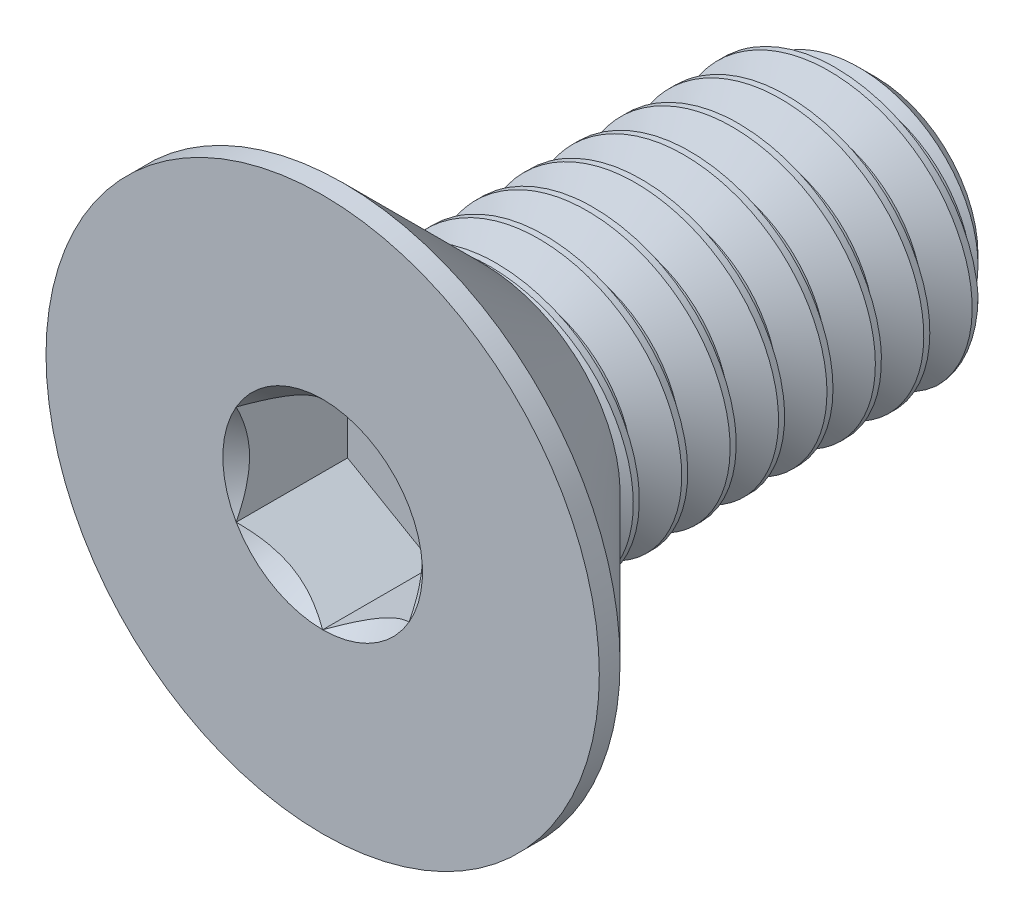
SolidWorks part; units mm, degrees
ref_plane "Front" through (0, 0, 0) normal (0, 0, 1) x (1, 0, 0)
ref_plane "Top" through (0, 0, 0) normal (0, 1, 0) x (1, 0, 0)
ref_plane "Right" through (0, 0, 0) normal (1, 0, 0) x (0, 0, -1)
sketch "Sketch1" plane through (0, 0, 0) normal (1, 0, 0) x (0, 0, -1)
  line L0 (0, 4) -> (0.3, 4) construction
  line L1 (0.3, 4) -> (2.3, 2) construction
  line L2 (0, 2) -> (8, 2)
  line L3 (8, 2) -> (8, 0)
  line L4 (8, 0) -> (0, 0)
  line L5 (0, 0) -> (0, 4) construction
  line L6 (0, 4) -> (0, -4) construction
  line L7 (8, 2) -> (8, -2) construction
  line L8 (0, -4) -> (0.3, -4) construction
  line L9 (0.3, -4) -> (2.3, -2) construction
  line L11 (0, 2) -> (0, 0)
  line L12 (2.3, 2) -> (2.3, 0) construction
revolve "Revolve1" add sketch "Sketch1" angle 360 mid plane about L4
sketch "Sketch3" plane through (0, 0, -8) normal (0, 0, -1) x (-1, 0, 0)
  circle A0 centre (0, 0) radius 2
curve "Helix/Spiral1" pitch 0.7 height 8 radius 2 centre (0, 0, -8) axis (0, 0, 1) start towards (0, 1, 0)
sketch "Sketch2" plane through (0, 0, 0) normal (1, 0, 0) x (0, 0, -1)
  line L0 (8, 2) -> (8.6125, 2)
  line L1 (8.6125, 2) -> (8.35, 1.5453)
  line L2 (8.35, 1.5453) -> (8.2625, 1.5453)
  line L3 (8.2625, 1.5453) -> (8, 2)
  line L4 (8.1312, 1.7727) -> (8.4812, 1.7727) construction
  dimension "D1" = 60
  dimension "D2" = 0.0875
  dimension "D3" = 0.35
chamfer "Chamfer1" distance 0.525 angle 45 1 edges at (0, 2, -8)
sweep "Cut-Sweep1" cut profiles "Sketch2" path "Helix/Spiral1" align with end faces yes
sketch "Sketch7" plane through (0, 0, 0) normal (1, 0, 0) x (0, 0, -1)
  line L0 (0, 4) -> (0.3, 4) construction
  line L1 (0.3, 4) -> (2.3, 2) construction
  line L2 (0, 4) -> (0.3, 4)
  line L3 (0.3, 4) -> (2.3, 2)
  line L4 (2.3, 2) -> (2.3, 0) construction
  line L5 (2.3, 2) -> (2.3, 0)
  line L7 (0, 0) -> (0, 4) construction
  line L8 (0, 0) -> (0, 4)
  line L9 (0, 0) -> (2.3, 0)
  line L10 (4.4, 0) -> (-4.4, 0) construction
revolve "Revolve2" add sketch "Sketch7" angle 360 mid plane about L9
ref_plane "Plane1" through (0, 0, -2.3) normal (0, 0, 1) x (1, 0, 0)
sketch "Sketch8" plane through (0, 0, -2.3) normal (0, 0, 1) x (1, 0, 0)
  circle A0 centre (0, 0) radius 2
extrude "Boss-Extrude1" add sketch "Sketch8" against normal through all draft 45
sketch "Sketch5" plane through (0, 0, 0) normal (0, 0, 1) x (1, 0, 0)
  line L1 (1.25, -0.7217) -> (1.25, 0.7217)
  line L2 (1.25, 0.7217) -> (0, 1.4434)
  line L3 (0, 1.4434) -> (-1.25, 0.7217)
  line L4 (-1.25, 0.7217) -> (-1.25, -0.7217)
  line L5 (-1.25, -0.7217) -> (0, -1.4434)
  line L6 (0, -1.4434) -> (1.25, -0.7217)
  circle A0 centre (0, 0) radius 1.25 construction
  dimension "Hex" = 2.5
extrude "Cut-Extrude2" cut sketch "Sketch5" against normal blind 1.61
sketch "Sketch6" plane through (0, 0, 0) normal (0, 0, 1) x (1, 0, 0)
  circle A0 centre (0, 0) radius 1.4434
extrude "Cut-Extrude3" cut sketch "Sketch6" against normal blind 1.61 draft 45
sketch "Sketch9" [suppressed] plane through (0, 0, -1.5) normal (0, 0, 1) x (1, 0, 0)
  circle A1 centre (0, 0) radius 1.25
  circle A2 centre (0, 0) radius 1.25
  point P0 (0, 1.25)
  dimension "D1" = 0
extrude "Boss-Extrude2" [suppressed] add sketch "Sketch9" against normal offset from surface (3.5 mm away) 26 up to face at (0, 1.475, -8)
fillet "Fillet1" [suppressed] radius 0.4
sketch "Sketch10" plane through (0, 0, 0) normal (1, 0, 0) x (0, 0, -1)
  line L0 (8, 2) -> (8, -2) construction
  point P0 (6.95, -2)
  dimension "D1" = 1.05
equation "\"D3@Helix/Spiral1\" = \"Lg@Sketch1\""
equation "\"D2@Sketch2\" = \"D4@Helix/Spiral1\" * .125"
equation "\"D3@Sketch2\" = \"D4@Helix/Spiral1\" * .5"
equation "\"D1@Chamfer1\" = \"D4@Helix/Spiral1\" * .75"
equation "\"D1@Cut-Extrude2\" = \"Head Ht@Sketch1\" * .7"
equation "\"D1@Sketch10\" = \"D4@Helix/Spiral1\" * 1.5"
equation "\"D1@Cut-Extrude3\" = \"D1@Cut-Extrude2\""
equation "\"D1@Fillet1\" = \"Dia@Sketch1\" * .1"
